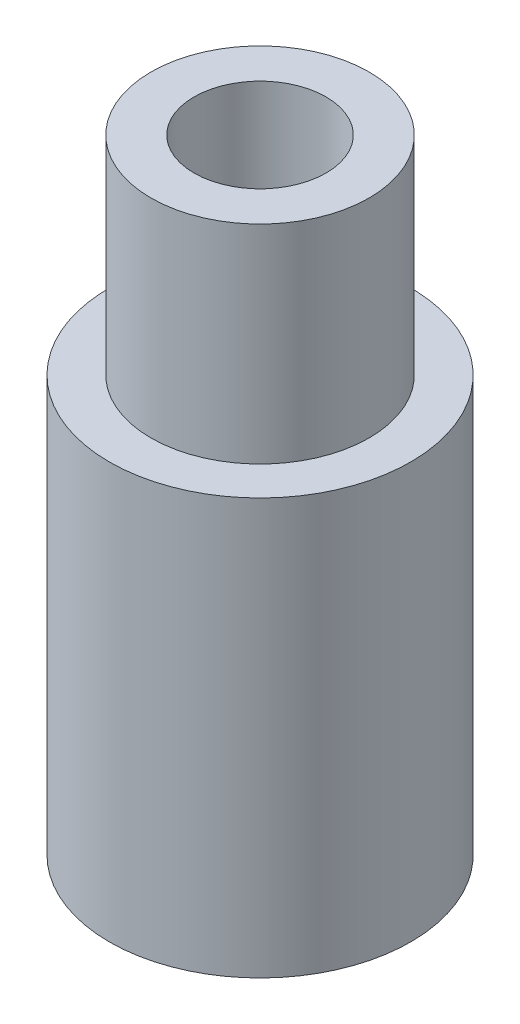
SolidWorks part; units mm, degrees
ref_plane "Front Plane" through (0, 0, 0) normal (0, 0, 1) x (1, 0, 0)
ref_plane "Top Plane" through (0, 0, 0) normal (0, 1, 0) x (1, 0, 0)
ref_plane "Right Plane" through (0, 0, 0) normal (1, 0, 0) x (0, 0, -1)
sketch "Sketch1" plane through (0, 0, 0) normal (0, 1, 0) x (1, 0, 0)
  circle A0 centre (0, 0) radius 3.175
  circle A1 centre (0, 0) radius 7.25
  dimension "D1" = 6.35
  dimension "D2" = 14.5
extrude "Boss-Extrude1" add sketch "Sketch1" along normal blind 30
sketch "Sketch2" plane through (0, 30, 0) normal (0, 1, 0) x (1, 0, 0)
  circle A0 centre (0, 0) radius 5.25
  dimension "D1" = 10.5
extrude "Cut-Extrude1" cut sketch "Sketch2" against normal blind 10 flip side to cut
sketch "Sketch3" plane through (0, 0, 0) normal (0, -1, 0) x (1, 0, 0)
  circle A1 centre (0, 0) radius 5.25
  dimension "D1" = 10.5
extrude "Cut-Extrude2" cut sketch "Sketch3" against normal blind 9
